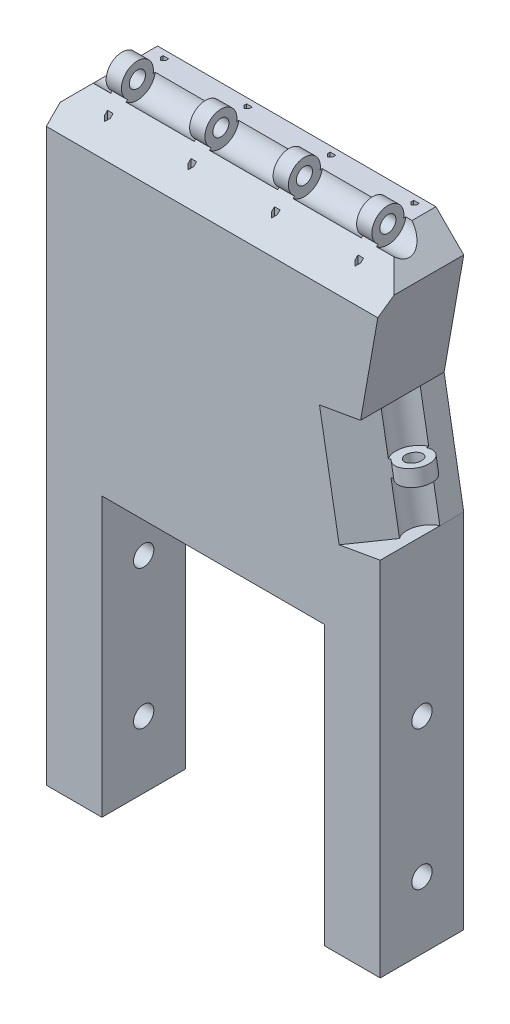
SolidWorks part; units mm, degrees
material "Custom Plastic"
ref_plane "Front Plane" through (0, 0, 0) normal (0, 0, 1) x (1, 0, 0)
ref_plane "Top Plane" through (0, 0, 0) normal (0, 1, 0) x (1, 0, 0)
ref_plane "Right Plane" through (0, 0, 0) normal (1, 0, 0) x (0, 0, -1)
sketch "Sketch1" plane through (0, 0, 0) normal (0, 0, 1) x (1, 0, 0)
  line L1 (-30, -30) -> (30, -30)
  line L2 (-30, -30) -> (-30, 30)
  line L3 (-30, 30) -> (30, 30)
  line L4 (30, -30) -> (30, 30)
  line L5 (-30, -30) -> (30, 30) construction
  line L6 (-30, 30) -> (30, -30) construction
  point P0 (0, 0)
  dimension "D1" = 60
  dimension "D2" = 60
extrude "Boss-Extrude1" add sketch "Sketch1" along normal mid plane 15
sketch "Sketch2" plane through (0, 0, 0) normal (0, 0, 1) x (1, 0, 0)
  line L0 (-30, 25) -> (-25, 30)
  line L1 (-30, 30) -> (-30, -30) construction
  line L2 (30, 30) -> (-30, 30) construction
  line L3 (-25, 30) -> (25, 30)
  line L4 (25, 30) -> (30, 25)
  line L5 (30, -30) -> (30, 30) construction
  line L10 (-30, -30) -> (30, -30) construction
  line L11 (14.5979, -30) -> (-15, -30)
  line L13 (-30, -15) -> (-30, 25)
  line L15 (-30, -15) -> (-30, -30)
  line L16 (-30, -30) -> (-15, -30)
  line L17 (14.5979, -30) -> (30, -30)
  line L18 (30, -30) -> (30, -15)
  line L19 (30, 25) -> (26.4735, 5)
  line L20 (26.4735, 5) -> (30, -15)
  dimension "D1" = 5
  dimension "D2" = 5
  dimension "D3" = 5
  dimension "D4" = 5
  dimension "D5" = 170
  dimension "D6" = 20
  dimension "D7" = 15
extrude "Cut-Extrude6" cut sketch "Sketch2" against normal through all both and the other way through all flip side to cut
ref_plane "Plane1" through (29.5, 0, 0) normal (1, 0, 0) x (0, 0, -1)
sketch "Sketch9" plane through (0, 0, 0) normal (1, 0, 0) x (0, 0, -1)
  line L0 (-7.5, 30) -> (0, 30)
  line L1 (7.5, 30) -> (-7.5, 30) construction
  line L7 (0, 30) -> (-7.5, 22.5)
  line L8 (-7.5, 5) -> (-7.5, 25) construction
  line L9 (-7.5, 22.5) -> (-7.5, 30)
  dimension "D1" = 45
  dimension "D2" = 7.5
extrude "Cut-Extrude7" cut sketch "Sketch9" against normal through all both and the other way through all
sketch "Sketch25" plane through (0, -30, 0) normal (0, -1, 0) x (1, 0, 0)
  line L0 (-30, 7.5) -> (30, 7.5) construction
  line L1 (-30, -7.5) -> (-20, -7.5)
  line L2 (-30, -7.5) -> (-30, 7.5)
  line L3 (-30, 7.5) -> (-20, 7.5)
  line L4 (-20, -7.5) -> (-20, 7.5)
  line L5 (-30, -7.5) -> (-20, 7.5) construction
  line L6 (-30, 7.5) -> (-20, -7.5) construction
  line L8 (0, -8.25) -> (0, 8.25) construction
  line L9 (30, 7.5) -> (20, 7.5)
  line L10 (20, -7.5) -> (20, 7.5)
  line L11 (30, -7.5) -> (20, -7.5)
  line L12 (30, -7.5) -> (30, 7.5)
  point P0 (-25, 0)
  dimension "D1" = 15
  dimension "D2" = 10
  dimension "D3" = 20
extrude "Boss-Extrude5" add sketch "Sketch25" along normal blind 50
sketch "Sketch26" plane through (-20, 0, 0) normal (1, 0, 0) x (0, 0, -1)
  line L5 (7.5, -80) -> (-7.5, -80) construction
  circle A0 centre (0, -68) radius 1.825
  circle A1 centre (0, -43) radius 1.825
  dimension "D1" = 3.65
  dimension "D2" = 3.65
  dimension "D3" = 12
  dimension "D4" = 25
extrude "Cut-Extrude22" cut sketch "Sketch26" against normal through all both and the other way through all
ref_plane "Plane4" through (-22.5, 0, 0) normal (-1, 0, 0) x (0, 0, 1)
sketch "Sketch28" plane through (-22.5, 0, 0) normal (-1, 0, 0) x (0, 0, 1)
  circle A0 centre (0, 30.5) radius 2.875
  dimension "D2" = 5.75
  dimension "D1" = 0.5
extrude "Boss-Extrude6" add sketch "Sketch28" along normal mid plane 2.75
pattern_linear "LPattern1" count 4 spacing 15 along (1, 0, 0) of "Boss-Extrude6"
sketch "Sketch29" plane through (-21.125, 0, 0) normal (1, 0, 0) x (0, 0, -1)
  circle A0 centre (0, 30.5) radius 3.25
  dimension "D1" = 6.5
extrude "Cut-Extrude23" cut sketch "Sketch29" along normal blind 12.25
mirror "Mirror1" about plane through (-22.5, 0, 0) normal (-1, 0, 0) of "Cut-Extrude23"
pattern_linear "LPattern2" count 4 spacing 15 along (1, 0, 0) of "Cut-Extrude23"
ref_plane "Plane5" through (1.7065, -9.678, 0) normal (-0.1736, 0.9848, 0) x (0.9848, 0.1736, 0)
sketch "Sketch31" plane through (1.7065, -9.678, 0) normal (-0.1736, 0.9848, 0) x (0.9848, 0.1736, 0)
  line L0 (26.9395, -7.5) -> (19.4395, -7.5)
  line L1 (19.4395, -7.5) -> (26.9395, 0)
  line L2 (26.9395, 0) -> (26.9395, -7.5)
  line L7 (26.9395, 7.5) -> (26.9395, -7.5) construction
  line L8 (26.9395, -7.5) -> (33.0172, -7.5) construction
  dimension "D1" = 45
  dimension "D2" = 7.5
extrude "Cut-Extrude25" cut sketch "Sketch31" against normal up to vertex (10.1543 mm away) and the other way up to vertex (10.1543 mm away) up to point (30, -15, 7.5) other way up to point (26.4735, 5, -7.5)
sketch "Sketch32" plane through (1.7065, -9.678, 0) normal (-0.1736, 0.9848, 0) x (0.9848, 0.1736, 0)
  circle A0 centre (27.4395, 0) radius 2.875
  dimension "D2" = 5.75
  dimension "D1" = 0.5
extrude "Boss-Extrude7" add sketch "Sketch32" along normal mid plane 2.75
sketch "Sketch33" plane through (1.9453, -11.0321, 0) normal (0.1736, -0.9848, 0) x (0.9848, 0.1736, 0)
  circle A0 centre (27.4395, 0) radius 3.25
  dimension "D1" = 6.5
extrude "Cut-Extrude26" cut sketch "Sketch33" along normal up to vertex (8.7793 mm away) up to point (30, -15, 0)
mirror "Mirror2" about plane through (1.7065, -9.678, 0) normal (-0.1736, 0.9848, 0) of "Cut-Extrude26"
sketch "Sketch34" plane through (1.9453, -11.0321, 0) normal (0.1736, -0.9848, 0) x (0.9848, 0.1736, 0)
  circle A0 centre (27.4395, 0) radius 1.45
  dimension "D1" = 2.9
extrude "Cut-Extrude27" cut sketch "Sketch34" against normal up to surface (2.75 mm away) up to face at (27.6908, -3.7, -0.316)
sketch "Sketch35" plane through (23.875, 0, 0) normal (1, 0, 0) x (0, 0, -1)
  circle A0 centre (0, 30.5) radius 1.45
  dimension "D1" = 2.9
extrude "Cut-Extrude28" cut sketch "Sketch35" against normal up to surface (47.75 mm away) up to face at (-23.875, 29.6881, -0.316)
sketch "Sketch36" plane through (0, -30, 0) normal (0, -1, 0) x (1, 0, 0)
  line L0 (0, 6.5) -> (-2, 4.5)
  line L1 (-2, 4.5) -> (-2, 2.5)
  line L2 (-2, 2.5) -> (2, 2.5)
  line L3 (2, 2.5) -> (2, 4.5)
  line L4 (2, 4.5) -> (0, 6.5)
  line L5 (-20, 7.5) -> (20, 7.5) construction
  point P8 (0, 7.5)
  dimension "D1" = 2
  dimension "D2" = 135
  dimension "D3" = 2
  dimension "D4" = 135
  dimension "D5" = 4
  dimension "D6" = 1
extrude "Cut-Extrude29" cut sketch "Sketch36" against normal up to surface (30 mm away) up to plane "Top Plane"
pattern_linear "LPattern3" count 2 spacing 9 along (0, 0, -1) of "Cut-Extrude29"
sketch "Sketch41" plane through (0, 30, 0) normal (0, 1, 0) x (1, 0, 0)
  line L0 (-23, 6.5) -> (-22, 6.5)
  line L1 (-22, 6.5) -> (-22, 6)
  line L2 (-22, 6) -> (-22.5, 5.5)
  line L3 (-22.5, 8.25) -> (-22.5, -8.25) construction
  line L4 (-22.5, 5.5) -> (-23, 6)
  line L5 (-23, 6) -> (-23, 6.5)
  line L6 (25, 7.5) -> (-25, 7.5) construction
  line L7 (-8, 6) -> (-8, 6.5)
  line L8 (-8, 6.5) -> (-7, 6.5)
  line L9 (-7, 6.5) -> (-7, 6)
  line L10 (-7, 6) -> (-7.5, 5.5)
  line L11 (-7.5, 5.5) -> (-8, 6)
  line L12 (7, 6) -> (7, 6.5)
  line L13 (7, 6.5) -> (8, 6.5)
  line L14 (8, 6.5) -> (8, 6)
  line L15 (8, 6) -> (7.5, 5.5)
  line L16 (7.5, 5.5) -> (7, 6)
  line L17 (22, 6) -> (22, 6.5)
  line L18 (22, 6.5) -> (23, 6.5)
  line L19 (23, 6.5) -> (23, 6)
  line L20 (23, 6) -> (22.5, 5.5)
  line L21 (22.5, 5.5) -> (22, 6)
  line L22 (-8, -4) -> (-8, -3.5)
  line L23 (-8, -3.5) -> (-7, -3.5)
  line L24 (-7, -3.5) -> (-7, -4)
  line L25 (-7, -4) -> (-7.5, -4.5)
  line L26 (-7.5, -4.5) -> (-8, -4)
  line L27 (7, -4) -> (7, -3.5)
  line L28 (7, -3.5) -> (8, -3.5)
  line L29 (8, -3.5) -> (8, -4)
  line L30 (8, -4) -> (7.5, -4.5)
  line L31 (7.5, -4.5) -> (7, -4)
  line L32 (22, -4) -> (22, -3.5)
  line L33 (22, -3.5) -> (23, -3.5)
  line L34 (23, -3.5) -> (23, -4)
  line L35 (23, -4) -> (22.5, -4.5)
  line L36 (22.5, -4.5) -> (22, -4)
  line L37 (-23, -4) -> (-23, -3.5)
  line L38 (-23, -3.5) -> (-22, -3.5)
  line L39 (-22, -3.5) -> (-22, -4)
  line L40 (-22, -4) -> (-22.5, -4.5)
  line L41 (-22.5, -4.5) -> (-23, -4)
  dimension "D1" = 0.5
  dimension "D2" = 0.5
  dimension "D3" = 135
  dimension "D4" = 1
  dimension "D5" = 1
  dimension "D8" = 9
  dimension "D6" = 4
  dimension "D7" = 2
extrude "Cut-Extrude32" cut sketch "Sketch41" against normal blind 10
ref_plane "Plane6" through (-11, 11, 0) normal (-0.7071, 0.7071, 0) x (0.7071, 0.7071, 0)
sketch "Sketch42" plane through (-11, 11, 0) normal (-0.7071, 0.7071, 0) x (0.7071, 0.7071, 0)
  line L0 (-0.9221, -4.5) -> (-1.4142, -4.0079)
  line L1 (-1.4142, -4.0079) -> (-1.4142, -3.5079)
  line L2 (-1.4142, -3.5079) -> (-0.4142, -3.4921)
  line L3 (-0.4142, -3.4921) -> (-0.4142, -3.9921)
  line L4 (-0.4142, -3.9921) -> (-0.9221, -4.5)
  line L5 (-5.3033, -7.5) -> (-77.7817, -7.5) construction
  line L10 (-1.4142, -4) -> (-1.4142, -3.5) construction
  dimension "D1" = 135
  dimension "D2" = 135
  dimension "D3" = 1
  dimension "D4" = 0.5
  dimension "D5" = 0.5
  dimension "D6" = 90.902
  dimension "D7" = 3
extrude "Cut-Extrude34" cut sketch "Sketch42" against normal up to surface and the other way up to surface up to face at (2, -15, 3.5) other way up to plane "Plane4"
